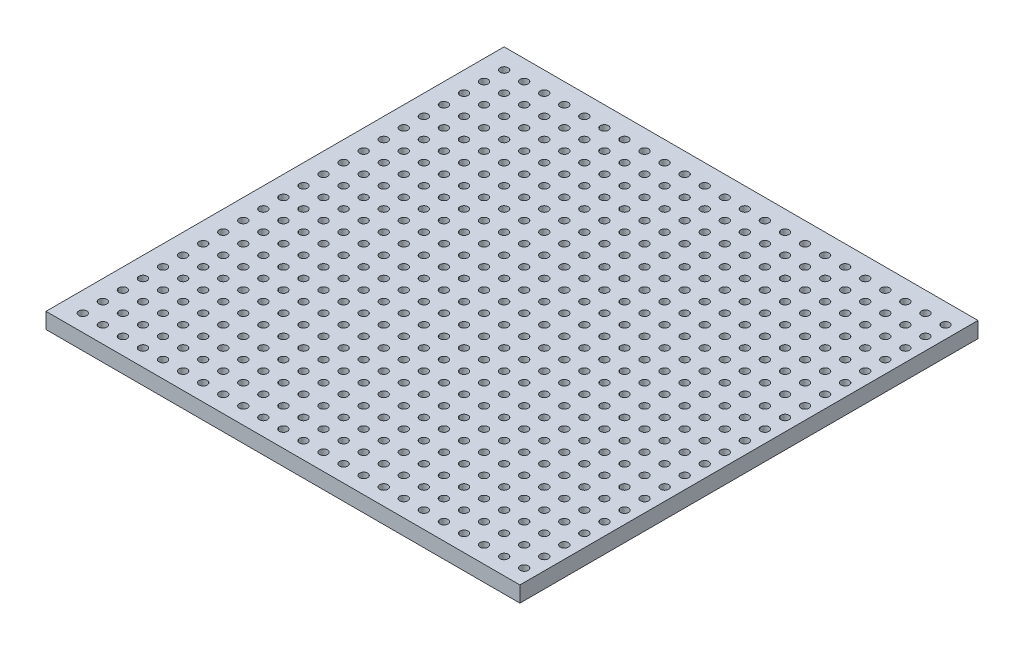
SolidWorks part; units mm, degrees
ref_plane "Front Plane" through (0, 0, 0) normal (0, 0, 1) x (1, 0, 0)
ref_plane "Top Plane" through (0, 0, 0) normal (0, 1, 0) x (1, 0, 0)
ref_plane "Right Plane" through (0, 0, 0) normal (1, 0, 0) x (0, 0, -1)
sketch "Sketch1" plane through (0, 0, 0) normal (0, 1, 0) x (1, 0, 0)
  line L1 (-30, -29) -> (30, -29)
  line L2 (-30, -29) -> (-30, 29)
  line L3 (-30, 29) -> (30, 29)
  line L4 (30, -29) -> (30, 29)
  line L5 (-30, -29) -> (30, 29) construction
  line L6 (-30, 29) -> (30, -29) construction
  point P0 (0, 0)
  dimension "D1" = 58
  dimension "D2" = 60
extrude "Boss-Extrude1" add sketch "Sketch1" along normal blind 2
sketch "Sketch2" plane through (0, 2, 0) normal (0, 1, 0) x (1, 0, 0)
  line L0 (30, 29) -> (-30, 29) construction
  line L1 (-30, 29) -> (-30, -29) construction
  line L2 (-27.46, 26.46) -> (-27.46, -29) construction
  line L3 (-30, -29) -> (30, -29) construction
  circle A0 centre (-27.46, 26.46) radius 0.51
  circle A1 centre (-27.46, 23.92) radius 0.51
  circle A2 centre (-27.46, 21.38) radius 0.51
  circle A3 centre (-27.46, 18.84) radius 0.51
  circle A4 centre (-27.46, 16.3) radius 0.51
  circle A5 centre (-27.46, 13.76) radius 0.51
  circle A6 centre (-27.46, 11.22) radius 0.51
  circle A7 centre (-27.46, 8.68) radius 0.51
  circle A8 centre (-27.46, 6.14) radius 0.51
  circle A9 centre (-27.46, 3.6) radius 0.51
  circle A10 centre (-27.46, 1.06) radius 0.51
  circle A11 centre (-27.46, -1.48) radius 0.51
  circle A12 centre (-24.92, 26.46) radius 0.51
  circle A13 centre (-24.92, 23.92) radius 0.51
  circle A14 centre (-24.92, 21.38) radius 0.51
  circle A15 centre (-24.92, 18.84) radius 0.51
  circle A16 centre (-24.92, 16.3) radius 0.51
  circle A17 centre (-24.92, 13.76) radius 0.51
  circle A18 centre (-24.92, 11.22) radius 0.51
  circle A19 centre (-24.92, 8.68) radius 0.51
  circle A20 centre (-24.92, 6.14) radius 0.51
  circle A21 centre (-24.92, 3.6) radius 0.51
  circle A22 centre (-24.92, 1.06) radius 0.51
  circle A23 centre (-24.92, -1.48) radius 0.51
  circle A24 centre (-22.38, 26.46) radius 0.51
  circle A25 centre (-22.38, 23.92) radius 0.51
  circle A26 centre (-22.38, 21.38) radius 0.51
  circle A27 centre (-22.38, 18.84) radius 0.51
  circle A28 centre (-22.38, 16.3) radius 0.51
  circle A29 centre (-22.38, 13.76) radius 0.51
  circle A30 centre (-22.38, 11.22) radius 0.51
  circle A31 centre (-22.38, 8.68) radius 0.51
  circle A32 centre (-22.38, 6.14) radius 0.51
  circle A33 centre (-22.38, 3.6) radius 0.51
  circle A34 centre (-22.38, 1.06) radius 0.51
  circle A35 centre (-22.38, -1.48) radius 0.51
  circle A36 centre (-19.84, 26.46) radius 0.51
  circle A37 centre (-19.84, 23.92) radius 0.51
  circle A38 centre (-19.84, 21.38) radius 0.51
  circle A39 centre (-19.84, 18.84) radius 0.51
  circle A40 centre (-19.84, 16.3) radius 0.51
  circle A41 centre (-19.84, 13.76) radius 0.51
  circle A42 centre (-19.84, 11.22) radius 0.51
  circle A43 centre (-19.84, 8.68) radius 0.51
  circle A44 centre (-19.84, 6.14) radius 0.51
  circle A45 centre (-19.84, 3.6) radius 0.51
  circle A46 centre (-19.84, 1.06) radius 0.51
  circle A47 centre (-19.84, -1.48) radius 0.51
  circle A48 centre (-17.3, 26.46) radius 0.51
  circle A49 centre (-17.3, 23.92) radius 0.51
  circle A50 centre (-17.3, 21.38) radius 0.51
  circle A51 centre (-17.3, 18.84) radius 0.51
  circle A52 centre (-17.3, 16.3) radius 0.51
  circle A53 centre (-17.3, 13.76) radius 0.51
  circle A54 centre (-17.3, 11.22) radius 0.51
  circle A55 centre (-17.3, 8.68) radius 0.51
  circle A56 centre (-17.3, 6.14) radius 0.51
  circle A57 centre (-17.3, 3.6) radius 0.51
  circle A58 centre (-17.3, 1.06) radius 0.51
  circle A59 centre (-17.3, -1.48) radius 0.51
  circle A60 centre (-14.76, 26.46) radius 0.51
  circle A61 centre (-14.76, 23.92) radius 0.51
  circle A62 centre (-14.76, 21.38) radius 0.51
  circle A63 centre (-14.76, 18.84) radius 0.51
  circle A64 centre (-14.76, 16.3) radius 0.51
  circle A65 centre (-14.76, 13.76) radius 0.51
  circle A66 centre (-14.76, 11.22) radius 0.51
  circle A67 centre (-14.76, 8.68) radius 0.51
  circle A68 centre (-14.76, 6.14) radius 0.51
  circle A69 centre (-14.76, 3.6) radius 0.51
  circle A70 centre (-14.76, 1.06) radius 0.51
  circle A71 centre (-14.76, -1.48) radius 0.51
  circle A72 centre (-12.22, 26.46) radius 0.51
  circle A73 centre (-12.22, 23.92) radius 0.51
  circle A74 centre (-12.22, 21.38) radius 0.51
  circle A75 centre (-12.22, 18.84) radius 0.51
  circle A76 centre (-12.22, 16.3) radius 0.51
  circle A77 centre (-12.22, 13.76) radius 0.51
  circle A78 centre (-12.22, 11.22) radius 0.51
  circle A79 centre (-12.22, 8.68) radius 0.51
  circle A80 centre (-12.22, 6.14) radius 0.51
  circle A81 centre (-12.22, 3.6) radius 0.51
  circle A82 centre (-12.22, 1.06) radius 0.51
  circle A83 centre (-12.22, -1.48) radius 0.51
  circle A84 centre (-9.68, 26.46) radius 0.51
  circle A85 centre (-9.68, 23.92) radius 0.51
  circle A86 centre (-9.68, 21.38) radius 0.51
  circle A87 centre (-9.68, 18.84) radius 0.51
  circle A88 centre (-9.68, 16.3) radius 0.51
  circle A89 centre (-9.68, 13.76) radius 0.51
  circle A90 centre (-9.68, 11.22) radius 0.51
  circle A91 centre (-9.68, 8.68) radius 0.51
  circle A92 centre (-9.68, 6.14) radius 0.51
  circle A93 centre (-9.68, 3.6) radius 0.51
  circle A94 centre (-9.68, 1.06) radius 0.51
  circle A95 centre (-9.68, -1.48) radius 0.51
  circle A96 centre (-7.14, 26.46) radius 0.51
  circle A97 centre (-7.14, 23.92) radius 0.51
  circle A98 centre (-7.14, 21.38) radius 0.51
  circle A99 centre (-7.14, 18.84) radius 0.51
  circle A100 centre (-7.14, 16.3) radius 0.51
  circle A101 centre (-7.14, 13.76) radius 0.51
  circle A102 centre (-7.14, 11.22) radius 0.51
  circle A103 centre (-7.14, 8.68) radius 0.51
  circle A104 centre (-7.14, 6.14) radius 0.51
  circle A105 centre (-7.14, 3.6) radius 0.51
  circle A106 centre (-7.14, 1.06) radius 0.51
  circle A107 centre (-7.14, -1.48) radius 0.51
  circle A108 centre (-4.6, 26.46) radius 0.51
  circle A109 centre (-4.6, 23.92) radius 0.51
  circle A110 centre (-4.6, 21.38) radius 0.51
  circle A111 centre (-4.6, 18.84) radius 0.51
  circle A112 centre (-4.6, 16.3) radius 0.51
  circle A113 centre (-4.6, 13.76) radius 0.51
  circle A114 centre (-4.6, 11.22) radius 0.51
  circle A115 centre (-4.6, 8.68) radius 0.51
  circle A116 centre (-4.6, 6.14) radius 0.51
  circle A117 centre (-4.6, 3.6) radius 0.51
  circle A118 centre (-4.6, 1.06) radius 0.51
  circle A119 centre (-4.6, -1.48) radius 0.51
  circle A120 centre (-2.06, 26.46) radius 0.51
  circle A121 centre (-2.06, 23.92) radius 0.51
  circle A122 centre (-2.06, 21.38) radius 0.51
  circle A123 centre (-2.06, 18.84) radius 0.51
  circle A124 centre (-2.06, 16.3) radius 0.51
  circle A125 centre (-2.06, 13.76) radius 0.51
  circle A126 centre (-2.06, 11.22) radius 0.51
  circle A127 centre (-2.06, 8.68) radius 0.51
  circle A128 centre (-2.06, 6.14) radius 0.51
  circle A129 centre (-2.06, 3.6) radius 0.51
  circle A130 centre (-2.06, 1.06) radius 0.51
  circle A131 centre (-2.06, -1.48) radius 0.51
  circle A132 centre (0.48, 26.46) radius 0.51
  circle A133 centre (0.48, 23.92) radius 0.51
  circle A134 centre (0.48, 21.38) radius 0.51
  circle A135 centre (0.48, 18.84) radius 0.51
  circle A136 centre (0.48, 16.3) radius 0.51
  circle A137 centre (0.48, 13.76) radius 0.51
  circle A138 centre (0.48, 11.22) radius 0.51
  circle A139 centre (0.48, 8.68) radius 0.51
  circle A140 centre (0.48, 6.14) radius 0.51
  circle A141 centre (0.48, 3.6) radius 0.51
  circle A142 centre (0.48, 1.06) radius 0.51
  circle A143 centre (0.48, -1.48) radius 0.51
  circle A144 centre (3.02, 26.46) radius 0.51
  circle A145 centre (3.02, 23.92) radius 0.51
  circle A146 centre (3.02, 21.38) radius 0.51
  circle A147 centre (3.02, 18.84) radius 0.51
  circle A148 centre (3.02, 16.3) radius 0.51
  circle A149 centre (3.02, 13.76) radius 0.51
  circle A150 centre (3.02, 11.22) radius 0.51
  circle A151 centre (3.02, 8.68) radius 0.51
  circle A152 centre (3.02, 6.14) radius 0.51
  circle A153 centre (3.02, 3.6) radius 0.51
  circle A154 centre (3.02, 1.06) radius 0.51
  circle A155 centre (3.02, -1.48) radius 0.51
  circle A156 centre (5.56, 26.46) radius 0.51
  circle A157 centre (5.56, 23.92) radius 0.51
  circle A158 centre (5.56, 21.38) radius 0.51
  circle A159 centre (5.56, 18.84) radius 0.51
  circle A160 centre (5.56, 16.3) radius 0.51
  circle A161 centre (5.56, 13.76) radius 0.51
  circle A162 centre (5.56, 11.22) radius 0.51
  circle A163 centre (5.56, 8.68) radius 0.51
  circle A164 centre (5.56, 6.14) radius 0.51
  circle A165 centre (5.56, 3.6) radius 0.51
  circle A166 centre (5.56, 1.06) radius 0.51
  circle A167 centre (5.56, -1.48) radius 0.51
  circle A168 centre (8.1, 26.46) radius 0.51
  circle A169 centre (8.1, 23.92) radius 0.51
  circle A170 centre (8.1, 21.38) radius 0.51
  circle A171 centre (8.1, 18.84) radius 0.51
  circle A172 centre (8.1, 16.3) radius 0.51
  circle A173 centre (8.1, 13.76) radius 0.51
  circle A174 centre (8.1, 11.22) radius 0.51
  circle A175 centre (8.1, 8.68) radius 0.51
  circle A176 centre (8.1, 6.14) radius 0.51
  circle A177 centre (8.1, 3.6) radius 0.51
  circle A178 centre (8.1, 1.06) radius 0.51
  circle A179 centre (8.1, -1.48) radius 0.51
  circle A180 centre (10.64, 26.46) radius 0.51
  circle A181 centre (10.64, 23.92) radius 0.51
  circle A182 centre (10.64, 21.38) radius 0.51
  circle A183 centre (10.64, 18.84) radius 0.51
  circle A184 centre (10.64, 16.3) radius 0.51
  circle A185 centre (10.64, 13.76) radius 0.51
  circle A186 centre (10.64, 11.22) radius 0.51
  circle A187 centre (10.64, 8.68) radius 0.51
  circle A188 centre (10.64, 6.14) radius 0.51
  circle A189 centre (10.64, 3.6) radius 0.51
  circle A190 centre (10.64, 1.06) radius 0.51
  circle A191 centre (10.64, -1.48) radius 0.51
  circle A192 centre (13.18, 26.46) radius 0.51
  circle A193 centre (13.18, 23.92) radius 0.51
  circle A194 centre (13.18, 21.38) radius 0.51
  circle A195 centre (13.18, 18.84) radius 0.51
  circle A196 centre (13.18, 16.3) radius 0.51
  circle A197 centre (13.18, 13.76) radius 0.51
  circle A198 centre (13.18, 11.22) radius 0.51
  circle A199 centre (13.18, 8.68) radius 0.51
  circle A200 centre (13.18, 6.14) radius 0.51
  circle A201 centre (13.18, 3.6) radius 0.51
  circle A202 centre (13.18, 1.06) radius 0.51
  circle A203 centre (13.18, -1.48) radius 0.51
  circle A204 centre (15.72, 26.46) radius 0.51
  circle A205 centre (15.72, 23.92) radius 0.51
  circle A206 centre (15.72, 21.38) radius 0.51
  circle A207 centre (15.72, 18.84) radius 0.51
  circle A208 centre (15.72, 16.3) radius 0.51
  circle A209 centre (15.72, 13.76) radius 0.51
  circle A210 centre (15.72, 11.22) radius 0.51
  circle A211 centre (15.72, 8.68) radius 0.51
  circle A212 centre (15.72, 6.14) radius 0.51
  circle A213 centre (15.72, 3.6) radius 0.51
  circle A214 centre (15.72, 1.06) radius 0.51
  circle A215 centre (15.72, -1.48) radius 0.51
  circle A216 centre (18.26, 26.46) radius 0.51
  circle A217 centre (18.26, 23.92) radius 0.51
  circle A218 centre (18.26, 21.38) radius 0.51
  circle A219 centre (18.26, 18.84) radius 0.51
  circle A220 centre (18.26, 16.3) radius 0.51
  circle A221 centre (18.26, 13.76) radius 0.51
  circle A222 centre (18.26, 11.22) radius 0.51
  circle A223 centre (18.26, 8.68) radius 0.51
  circle A224 centre (18.26, 6.14) radius 0.51
  circle A225 centre (18.26, 3.6) radius 0.51
  circle A226 centre (18.26, 1.06) radius 0.51
  circle A227 centre (18.26, -1.48) radius 0.51
  circle A228 centre (20.8, 26.46) radius 0.51
  circle A229 centre (20.8, 23.92) radius 0.51
  circle A230 centre (20.8, 21.38) radius 0.51
  circle A231 centre (20.8, 18.84) radius 0.51
  circle A232 centre (20.8, 16.3) radius 0.51
  circle A233 centre (20.8, 13.76) radius 0.51
  circle A234 centre (20.8, 11.22) radius 0.51
  circle A235 centre (20.8, 8.68) radius 0.51
  circle A236 centre (20.8, 6.14) radius 0.51
  circle A237 centre (20.8, 3.6) radius 0.51
  circle A238 centre (20.8, 1.06) radius 0.51
  circle A239 centre (20.8, -1.48) radius 0.51
  circle A240 centre (23.34, 26.46) radius 0.51
  circle A241 centre (23.34, 23.92) radius 0.51
  circle A242 centre (23.34, 21.38) radius 0.51
  circle A243 centre (23.34, 18.84) radius 0.51
  circle A244 centre (23.34, 16.3) radius 0.51
  circle A245 centre (23.34, 13.76) radius 0.51
  circle A246 centre (23.34, 11.22) radius 0.51
  circle A247 centre (23.34, 8.68) radius 0.51
  circle A248 centre (23.34, 6.14) radius 0.51
  circle A249 centre (23.34, 3.6) radius 0.51
  circle A250 centre (23.34, 1.06) radius 0.51
  circle A251 centre (23.34, -1.48) radius 0.51
  circle A252 centre (25.88, 26.46) radius 0.51
  circle A253 centre (25.88, 23.92) radius 0.51
  circle A254 centre (25.88, 21.38) radius 0.51
  circle A255 centre (25.88, 18.84) radius 0.51
  circle A256 centre (25.88, 16.3) radius 0.51
  circle A257 centre (25.88, 13.76) radius 0.51
  circle A258 centre (25.88, 11.22) radius 0.51
  circle A259 centre (25.88, 8.68) radius 0.51
  circle A260 centre (25.88, 6.14) radius 0.51
  circle A261 centre (25.88, 3.6) radius 0.51
  circle A262 centre (25.88, 1.06) radius 0.51
  circle A263 centre (25.88, -1.48) radius 0.51
  circle A264 centre (28.42, 26.46) radius 0.51
  circle A265 centre (28.42, 23.92) radius 0.51
  circle A266 centre (28.42, 21.38) radius 0.51
  circle A267 centre (28.42, 18.84) radius 0.51
  circle A268 centre (28.42, 16.3) radius 0.51
  circle A269 centre (28.42, 13.76) radius 0.51
  circle A270 centre (28.42, 11.22) radius 0.51
  circle A271 centre (28.42, 8.68) radius 0.51
  circle A272 centre (28.42, 6.14) radius 0.51
  circle A273 centre (28.42, 3.6) radius 0.51
  circle A274 centre (28.42, 1.06) radius 0.51
  circle A275 centre (28.42, -1.48) radius 0.51
  circle A300 centre (33.5, 26.46) radius 0.51
  circle A301 centre (33.5, 23.92) radius 0.51
  circle A302 centre (33.5, 21.38) radius 0.51
  circle A303 centre (33.5, 18.84) radius 0.51
  circle A304 centre (33.5, 16.3) radius 0.51
  circle A305 centre (33.5, 13.76) radius 0.51
  circle A306 centre (33.5, 11.22) radius 0.51
  circle A307 centre (33.5, 8.68) radius 0.51
  circle A308 centre (33.5, 6.14) radius 0.51
  circle A309 centre (33.5, 3.6) radius 0.51
  circle A310 centre (33.5, 1.06) radius 0.51
  circle A311 centre (33.5, -1.48) radius 0.51
  circle A312 centre (30.96, 26.46) radius 0.51
  circle A313 centre (30.96, 23.92) radius 0.51
  circle A314 centre (30.96, 21.38) radius 0.51
  circle A315 centre (30.96, 18.84) radius 0.51
  circle A316 centre (30.96, 16.3) radius 0.51
  circle A317 centre (30.96, 13.76) radius 0.51
  circle A318 centre (30.96, 11.22) radius 0.51
  circle A319 centre (30.96, 8.68) radius 0.51
  circle A320 centre (30.96, 6.14) radius 0.51
  circle A321 centre (30.96, 3.6) radius 0.51
  circle A322 centre (30.96, 1.06) radius 0.51
  circle A323 centre (30.96, -1.48) radius 0.51
  circle A324 centre (-27.46, -4.02) radius 0.51
  circle A325 centre (-24.92, -4.02) radius 0.51
  circle A326 centre (-22.38, -4.02) radius 0.51
  circle A327 centre (-19.84, -4.02) radius 0.51
  circle A328 centre (-17.3, -4.02) radius 0.51
  circle A329 centre (-14.76, -4.02) radius 0.51
  circle A330 centre (-12.22, -4.02) radius 0.51
  circle A331 centre (-9.68, -4.02) radius 0.51
  circle A332 centre (-7.14, -4.02) radius 0.51
  circle A333 centre (-4.6, -4.02) radius 0.51
  circle A334 centre (-2.06, -4.02) radius 0.51
  circle A335 centre (0.48, -4.02) radius 0.51
  circle A336 centre (3.02, -4.02) radius 0.51
  circle A337 centre (5.56, -4.02) radius 0.51
  circle A338 centre (8.1, -4.02) radius 0.51
  circle A339 centre (10.64, -4.02) radius 0.51
  circle A340 centre (13.18, -4.02) radius 0.51
  circle A341 centre (15.72, -4.02) radius 0.51
  circle A342 centre (18.26, -4.02) radius 0.51
  circle A343 centre (20.8, -4.02) radius 0.51
  circle A344 centre (23.34, -4.02) radius 0.51
  circle A345 centre (25.88, -4.02) radius 0.51
  circle A346 centre (28.42, -4.02) radius 0.51
  circle A347 centre (-27.46, -6.56) radius 0.51
  circle A348 centre (-24.92, -6.56) radius 0.51
  circle A349 centre (-22.38, -6.56) radius 0.51
  circle A350 centre (-19.84, -6.56) radius 0.51
  circle A351 centre (-17.3, -6.56) radius 0.51
  circle A352 centre (-14.76, -6.56) radius 0.51
  circle A353 centre (-12.22, -6.56) radius 0.51
  circle A354 centre (-9.68, -6.56) radius 0.51
  circle A355 centre (-7.14, -6.56) radius 0.51
  circle A356 centre (-4.6, -6.56) radius 0.51
  circle A357 centre (-2.06, -6.56) radius 0.51
  circle A358 centre (0.48, -6.56) radius 0.51
  circle A359 centre (3.02, -6.56) radius 0.51
  circle A360 centre (5.56, -6.56) radius 0.51
  circle A361 centre (8.1, -6.56) radius 0.51
  circle A362 centre (10.64, -6.56) radius 0.51
  circle A363 centre (13.18, -6.56) radius 0.51
  circle A364 centre (15.72, -6.56) radius 0.51
  circle A365 centre (18.26, -6.56) radius 0.51
  circle A366 centre (20.8, -6.56) radius 0.51
  circle A367 centre (23.34, -6.56) radius 0.51
  circle A368 centre (25.88, -6.56) radius 0.51
  circle A369 centre (28.42, -6.56) radius 0.51
  circle A370 centre (-27.46, -9.1) radius 0.51
  circle A371 centre (-24.92, -9.1) radius 0.51
  circle A372 centre (-22.38, -9.1) radius 0.51
  circle A373 centre (-19.84, -9.1) radius 0.51
  circle A374 centre (-17.3, -9.1) radius 0.51
  circle A375 centre (-14.76, -9.1) radius 0.51
  circle A376 centre (-12.22, -9.1) radius 0.51
  circle A377 centre (-9.68, -9.1) radius 0.51
  circle A378 centre (-7.14, -9.1) radius 0.51
  circle A379 centre (-4.6, -9.1) radius 0.51
  circle A380 centre (-2.06, -9.1) radius 0.51
  circle A381 centre (0.48, -9.1) radius 0.51
  circle A382 centre (3.02, -9.1) radius 0.51
  circle A383 centre (5.56, -9.1) radius 0.51
  circle A384 centre (8.1, -9.1) radius 0.51
  circle A385 centre (10.64, -9.1) radius 0.51
  circle A386 centre (13.18, -9.1) radius 0.51
  circle A387 centre (15.72, -9.1) radius 0.51
  circle A388 centre (18.26, -9.1) radius 0.51
  circle A389 centre (20.8, -9.1) radius 0.51
  circle A390 centre (23.34, -9.1) radius 0.51
  circle A391 centre (25.88, -9.1) radius 0.51
  circle A392 centre (28.42, -9.1) radius 0.51
  circle A393 centre (-27.46, -11.64) radius 0.51
  circle A394 centre (-24.92, -11.64) radius 0.51
  circle A395 centre (-22.38, -11.64) radius 0.51
  circle A396 centre (-19.84, -11.64) radius 0.51
  circle A397 centre (-17.3, -11.64) radius 0.51
  circle A398 centre (-14.76, -11.64) radius 0.51
  circle A399 centre (-12.22, -11.64) radius 0.51
  circle A400 centre (-9.68, -11.64) radius 0.51
  circle A401 centre (-7.14, -11.64) radius 0.51
  circle A402 centre (-4.6, -11.64) radius 0.51
  circle A403 centre (-2.06, -11.64) radius 0.51
  circle A404 centre (0.48, -11.64) radius 0.51
  circle A405 centre (3.02, -11.64) radius 0.51
  circle A406 centre (5.56, -11.64) radius 0.51
  circle A407 centre (8.1, -11.64) radius 0.51
  circle A408 centre (10.64, -11.64) radius 0.51
  circle A409 centre (13.18, -11.64) radius 0.51
  circle A410 centre (15.72, -11.64) radius 0.51
  circle A411 centre (18.26, -11.64) radius 0.51
  circle A412 centre (20.8, -11.64) radius 0.51
  circle A413 centre (23.34, -11.64) radius 0.51
  circle A414 centre (25.88, -11.64) radius 0.51
  circle A415 centre (28.42, -11.64) radius 0.51
  circle A416 centre (-27.46, -14.18) radius 0.51
  circle A417 centre (-24.92, -14.18) radius 0.51
  circle A418 centre (-22.38, -14.18) radius 0.51
  circle A419 centre (-19.84, -14.18) radius 0.51
  circle A420 centre (-17.3, -14.18) radius 0.51
  circle A421 centre (-14.76, -14.18) radius 0.51
  circle A422 centre (-12.22, -14.18) radius 0.51
  circle A423 centre (-9.68, -14.18) radius 0.51
  circle A424 centre (-7.14, -14.18) radius 0.51
  circle A425 centre (-4.6, -14.18) radius 0.51
  circle A426 centre (-2.06, -14.18) radius 0.51
  circle A427 centre (0.48, -14.18) radius 0.51
  circle A428 centre (3.02, -14.18) radius 0.51
  circle A429 centre (5.56, -14.18) radius 0.51
  circle A430 centre (8.1, -14.18) radius 0.51
  circle A431 centre (10.64, -14.18) radius 0.51
  circle A432 centre (13.18, -14.18) radius 0.51
  circle A433 centre (15.72, -14.18) radius 0.51
  circle A434 centre (18.26, -14.18) radius 0.51
  circle A435 centre (20.8, -14.18) radius 0.51
  circle A436 centre (23.34, -14.18) radius 0.51
  circle A437 centre (25.88, -14.18) radius 0.51
  circle A438 centre (28.42, -14.18) radius 0.51
  circle A439 centre (-27.46, -16.72) radius 0.51
  circle A440 centre (-24.92, -16.72) radius 0.51
  circle A441 centre (-22.38, -16.72) radius 0.51
  circle A442 centre (-19.84, -16.72) radius 0.51
  circle A443 centre (-17.3, -16.72) radius 0.51
  circle A444 centre (-14.76, -16.72) radius 0.51
  circle A445 centre (-12.22, -16.72) radius 0.51
  circle A446 centre (-9.68, -16.72) radius 0.51
  circle A447 centre (-7.14, -16.72) radius 0.51
  circle A448 centre (-4.6, -16.72) radius 0.51
  circle A449 centre (-2.06, -16.72) radius 0.51
  circle A450 centre (0.48, -16.72) radius 0.51
  circle A451 centre (3.02, -16.72) radius 0.51
  circle A452 centre (5.56, -16.72) radius 0.51
  circle A453 centre (8.1, -16.72) radius 0.51
  circle A454 centre (10.64, -16.72) radius 0.51
  circle A455 centre (13.18, -16.72) radius 0.51
  circle A456 centre (15.72, -16.72) radius 0.51
  circle A457 centre (18.26, -16.72) radius 0.51
  circle A458 centre (20.8, -16.72) radius 0.51
  circle A459 centre (23.34, -16.72) radius 0.51
  circle A460 centre (25.88, -16.72) radius 0.51
  circle A461 centre (28.42, -16.72) radius 0.51
  circle A462 centre (-27.46, -19.26) radius 0.51
  circle A463 centre (-24.92, -19.26) radius 0.51
  circle A464 centre (-22.38, -19.26) radius 0.51
  circle A465 centre (-19.84, -19.26) radius 0.51
  circle A466 centre (-17.3, -19.26) radius 0.51
  circle A467 centre (-14.76, -19.26) radius 0.51
  circle A468 centre (-12.22, -19.26) radius 0.51
  circle A469 centre (-9.68, -19.26) radius 0.51
  circle A470 centre (-7.14, -19.26) radius 0.51
  circle A471 centre (-4.6, -19.26) radius 0.51
  circle A472 centre (-2.06, -19.26) radius 0.51
  circle A473 centre (0.48, -19.26) radius 0.51
  circle A474 centre (3.02, -19.26) radius 0.51
  circle A475 centre (5.56, -19.26) radius 0.51
  circle A476 centre (8.1, -19.26) radius 0.51
  circle A477 centre (10.64, -19.26) radius 0.51
  circle A478 centre (13.18, -19.26) radius 0.51
  circle A479 centre (15.72, -19.26) radius 0.51
  circle A480 centre (18.26, -19.26) radius 0.51
  circle A481 centre (20.8, -19.26) radius 0.51
  circle A482 centre (23.34, -19.26) radius 0.51
  circle A483 centre (25.88, -19.26) radius 0.51
  circle A484 centre (28.42, -19.26) radius 0.51
  circle A485 centre (-27.46, -21.8) radius 0.51
  circle A486 centre (-24.92, -21.8) radius 0.51
  circle A487 centre (-22.38, -21.8) radius 0.51
  circle A488 centre (-19.84, -21.8) radius 0.51
  circle A489 centre (-17.3, -21.8) radius 0.51
  circle A490 centre (-14.76, -21.8) radius 0.51
  circle A491 centre (-12.22, -21.8) radius 0.51
  circle A492 centre (-9.68, -21.8) radius 0.51
  circle A493 centre (-7.14, -21.8) radius 0.51
  circle A494 centre (-4.6, -21.8) radius 0.51
  circle A495 centre (-2.06, -21.8) radius 0.51
  circle A496 centre (0.48, -21.8) radius 0.51
  circle A497 centre (3.02, -21.8) radius 0.51
  circle A498 centre (5.56, -21.8) radius 0.51
  circle A499 centre (8.1, -21.8) radius 0.51
  circle A500 centre (10.64, -21.8) radius 0.51
  circle A501 centre (13.18, -21.8) radius 0.51
  circle A502 centre (15.72, -21.8) radius 0.51
  circle A503 centre (18.26, -21.8) radius 0.51
  circle A504 centre (20.8, -21.8) radius 0.51
  circle A505 centre (23.34, -21.8) radius 0.51
  circle A506 centre (25.88, -21.8) radius 0.51
  circle A507 centre (28.42, -21.8) radius 0.51
  circle A508 centre (-27.46, -24.34) radius 0.51
  circle A509 centre (-24.92, -24.34) radius 0.51
  circle A510 centre (-22.38, -24.34) radius 0.51
  circle A511 centre (-19.84, -24.34) radius 0.51
  circle A512 centre (-17.3, -24.34) radius 0.51
  circle A513 centre (-14.76, -24.34) radius 0.51
  circle A514 centre (-12.22, -24.34) radius 0.51
  circle A515 centre (-9.68, -24.34) radius 0.51
  circle A516 centre (-7.14, -24.34) radius 0.51
  circle A517 centre (-4.6, -24.34) radius 0.51
  circle A518 centre (-2.06, -24.34) radius 0.51
  circle A519 centre (0.48, -24.34) radius 0.51
  circle A520 centre (3.02, -24.34) radius 0.51
  circle A521 centre (5.56, -24.34) radius 0.51
  circle A522 centre (8.1, -24.34) radius 0.51
  circle A523 centre (10.64, -24.34) radius 0.51
  circle A524 centre (13.18, -24.34) radius 0.51
  circle A525 centre (15.72, -24.34) radius 0.51
  circle A526 centre (18.26, -24.34) radius 0.51
  circle A527 centre (20.8, -24.34) radius 0.51
  circle A528 centre (23.34, -24.34) radius 0.51
  circle A529 centre (25.88, -24.34) radius 0.51
  circle A530 centre (28.42, -24.34) radius 0.51
  circle A531 centre (-27.46, -26.88) radius 0.51
  circle A532 centre (-24.92, -26.88) radius 0.51
  circle A533 centre (-22.38, -26.88) radius 0.51
  circle A534 centre (-19.84, -26.88) radius 0.51
  circle A535 centre (-17.3, -26.88) radius 0.51
  circle A536 centre (-14.76, -26.88) radius 0.51
  circle A537 centre (-12.22, -26.88) radius 0.51
  circle A538 centre (-9.68, -26.88) radius 0.51
  circle A539 centre (-7.14, -26.88) radius 0.51
  circle A540 centre (-4.6, -26.88) radius 0.51
  circle A541 centre (-2.06, -26.88) radius 0.51
  circle A542 centre (0.48, -26.88) radius 0.51
  circle A543 centre (3.02, -26.88) radius 0.51
  circle A544 centre (5.56, -26.88) radius 0.51
  circle A545 centre (8.1, -26.88) radius 0.51
  circle A546 centre (10.64, -26.88) radius 0.51
  circle A547 centre (13.18, -26.88) radius 0.51
  circle A548 centre (15.72, -26.88) radius 0.51
  circle A549 centre (18.26, -26.88) radius 0.51
  circle A550 centre (20.8, -26.88) radius 0.51
  circle A551 centre (23.34, -26.88) radius 0.51
  circle A552 centre (25.88, -26.88) radius 0.51
  circle A553 centre (28.42, -26.88) radius 0.51
  circle A761 centre (-27.46, -29.42) radius 0.51
  circle A762 centre (-24.92, -29.42) radius 0.51
  circle A763 centre (-22.38, -29.42) radius 0.51
  circle A764 centre (-19.84, -29.42) radius 0.51
  circle A765 centre (-17.3, -29.42) radius 0.51
  circle A766 centre (-14.76, -29.42) radius 0.51
  circle A767 centre (-12.22, -29.42) radius 0.51
  circle A768 centre (-9.68, -29.42) radius 0.51
  circle A769 centre (-7.14, -29.42) radius 0.51
  circle A770 centre (-4.6, -29.42) radius 0.51
  circle A771 centre (-2.06, -29.42) radius 0.51
  circle A772 centre (0.48, -29.42) radius 0.51
  circle A773 centre (3.02, -29.42) radius 0.51
  circle A774 centre (5.56, -29.42) radius 0.51
  circle A775 centre (8.1, -29.42) radius 0.51
  circle A776 centre (10.64, -29.42) radius 0.51
  circle A777 centre (13.18, -29.42) radius 0.51
  circle A778 centre (15.72, -29.42) radius 0.51
  circle A779 centre (18.26, -29.42) radius 0.51
  circle A780 centre (20.8, -29.42) radius 0.51
  circle A781 centre (23.34, -29.42) radius 0.51
  circle A782 centre (25.88, -29.42) radius 0.51
  circle A783 centre (28.42, -29.42) radius 0.51
  circle A784 centre (-27.46, -31.96) radius 0.51
  circle A785 centre (-24.92, -31.96) radius 0.51
  circle A786 centre (-22.38, -31.96) radius 0.51
  circle A787 centre (-19.84, -31.96) radius 0.51
  circle A788 centre (-17.3, -31.96) radius 0.51
  circle A789 centre (-14.76, -31.96) radius 0.51
  circle A790 centre (-12.22, -31.96) radius 0.51
  circle A791 centre (-9.68, -31.96) radius 0.51
  circle A792 centre (-7.14, -31.96) radius 0.51
  circle A793 centre (-4.6, -31.96) radius 0.51
  circle A794 centre (-2.06, -31.96) radius 0.51
  circle A795 centre (0.48, -31.96) radius 0.51
  circle A796 centre (3.02, -31.96) radius 0.51
  circle A797 centre (5.56, -31.96) radius 0.51
  circle A798 centre (8.1, -31.96) radius 0.51
  circle A799 centre (10.64, -31.96) radius 0.51
  circle A800 centre (13.18, -31.96) radius 0.51
  circle A801 centre (15.72, -31.96) radius 0.51
  circle A802 centre (18.26, -31.96) radius 0.51
  circle A803 centre (20.8, -31.96) radius 0.51
  circle A804 centre (23.34, -31.96) radius 0.51
  circle A805 centre (25.88, -31.96) radius 0.51
  circle A806 centre (28.42, -31.96) radius 0.51
  circle A807 centre (-27.46, -34.5) radius 0.51
  circle A808 centre (-24.92, -34.5) radius 0.51
  circle A809 centre (-22.38, -34.5) radius 0.51
  circle A810 centre (-19.84, -34.5) radius 0.51
  circle A811 centre (-17.3, -34.5) radius 0.51
  circle A812 centre (-14.76, -34.5) radius 0.51
  circle A813 centre (-12.22, -34.5) radius 0.51
  circle A814 centre (-9.68, -34.5) radius 0.51
  circle A815 centre (-7.14, -34.5) radius 0.51
  circle A816 centre (-4.6, -34.5) radius 0.51
  circle A817 centre (-2.06, -34.5) radius 0.51
  circle A818 centre (0.48, -34.5) radius 0.51
  circle A819 centre (3.02, -34.5) radius 0.51
  circle A820 centre (5.56, -34.5) radius 0.51
  circle A821 centre (8.1, -34.5) radius 0.51
  circle A822 centre (10.64, -34.5) radius 0.51
  circle A823 centre (13.18, -34.5) radius 0.51
  circle A824 centre (15.72, -34.5) radius 0.51
  circle A825 centre (18.26, -34.5) radius 0.51
  circle A826 centre (20.8, -34.5) radius 0.51
  circle A827 centre (23.34, -34.5) radius 0.51
  circle A828 centre (25.88, -34.5) radius 0.51
  circle A829 centre (28.42, -34.5) radius 0.51
  circle A830 centre (-27.46, -37.04) radius 0.51
  circle A831 centre (-24.92, -37.04) radius 0.51
  circle A832 centre (-22.38, -37.04) radius 0.51
  circle A833 centre (-19.84, -37.04) radius 0.51
  circle A834 centre (-17.3, -37.04) radius 0.51
  circle A835 centre (-14.76, -37.04) radius 0.51
  circle A836 centre (-12.22, -37.04) radius 0.51
  circle A837 centre (-9.68, -37.04) radius 0.51
  circle A838 centre (-7.14, -37.04) radius 0.51
  circle A839 centre (-4.6, -37.04) radius 0.51
  circle A840 centre (-2.06, -37.04) radius 0.51
  circle A841 centre (0.48, -37.04) radius 0.51
  circle A842 centre (3.02, -37.04) radius 0.51
  circle A843 centre (5.56, -37.04) radius 0.51
  circle A844 centre (8.1, -37.04) radius 0.51
  circle A845 centre (10.64, -37.04) radius 0.51
  circle A846 centre (13.18, -37.04) radius 0.51
  circle A847 centre (15.72, -37.04) radius 0.51
  circle A848 centre (18.26, -37.04) radius 0.51
  circle A849 centre (20.8, -37.04) radius 0.51
  circle A850 centre (23.34, -37.04) radius 0.51
  circle A851 centre (25.88, -37.04) radius 0.51
  circle A852 centre (28.42, -37.04) radius 0.51
  circle A853 centre (-27.46, -39.58) radius 0.51
  circle A854 centre (-24.92, -39.58) radius 0.51
  circle A855 centre (-22.38, -39.58) radius 0.51
  circle A856 centre (-19.84, -39.58) radius 0.51
  circle A857 centre (-17.3, -39.58) radius 0.51
  circle A858 centre (-14.76, -39.58) radius 0.51
  circle A859 centre (-12.22, -39.58) radius 0.51
  circle A860 centre (-9.68, -39.58) radius 0.51
  circle A861 centre (-7.14, -39.58) radius 0.51
  circle A862 centre (-4.6, -39.58) radius 0.51
  circle A863 centre (-2.06, -39.58) radius 0.51
  circle A864 centre (0.48, -39.58) radius 0.51
  circle A865 centre (3.02, -39.58) radius 0.51
  circle A866 centre (5.56, -39.58) radius 0.51
  circle A867 centre (8.1, -39.58) radius 0.51
  circle A868 centre (10.64, -39.58) radius 0.51
  circle A869 centre (13.18, -39.58) radius 0.51
  circle A870 centre (15.72, -39.58) radius 0.51
  circle A871 centre (18.26, -39.58) radius 0.51
  circle A872 centre (20.8, -39.58) radius 0.51
  circle A873 centre (23.34, -39.58) radius 0.51
  circle A874 centre (25.88, -39.58) radius 0.51
  circle A875 centre (28.42, -39.58) radius 0.51
  circle A876 centre (-27.46, -42.12) radius 0.51
  circle A877 centre (-24.92, -42.12) radius 0.51
  circle A878 centre (-22.38, -42.12) radius 0.51
  circle A879 centre (-19.84, -42.12) radius 0.51
  circle A880 centre (-17.3, -42.12) radius 0.51
  circle A881 centre (-14.76, -42.12) radius 0.51
  circle A882 centre (-12.22, -42.12) radius 0.51
  circle A883 centre (-9.68, -42.12) radius 0.51
  circle A884 centre (-7.14, -42.12) radius 0.51
  circle A885 centre (-4.6, -42.12) radius 0.51
  circle A886 centre (-2.06, -42.12) radius 0.51
  circle A887 centre (0.48, -42.12) radius 0.51
  circle A888 centre (3.02, -42.12) radius 0.51
  circle A889 centre (5.56, -42.12) radius 0.51
  circle A890 centre (8.1, -42.12) radius 0.51
  circle A891 centre (10.64, -42.12) radius 0.51
  circle A892 centre (13.18, -42.12) radius 0.51
  circle A893 centre (15.72, -42.12) radius 0.51
  circle A894 centre (18.26, -42.12) radius 0.51
  circle A895 centre (20.8, -42.12) radius 0.51
  circle A896 centre (23.34, -42.12) radius 0.51
  circle A897 centre (25.88, -42.12) radius 0.51
  circle A898 centre (28.42, -42.12) radius 0.51
  circle A899 centre (-27.46, -44.66) radius 0.51
  circle A900 centre (-24.92, -44.66) radius 0.51
  circle A901 centre (-22.38, -44.66) radius 0.51
  circle A902 centre (-19.84, -44.66) radius 0.51
  circle A903 centre (-17.3, -44.66) radius 0.51
  circle A904 centre (-14.76, -44.66) radius 0.51
  circle A905 centre (-12.22, -44.66) radius 0.51
  circle A906 centre (-9.68, -44.66) radius 0.51
  circle A907 centre (-7.14, -44.66) radius 0.51
  circle A908 centre (-4.6, -44.66) radius 0.51
  circle A909 centre (-2.06, -44.66) radius 0.51
  circle A910 centre (0.48, -44.66) radius 0.51
  circle A911 centre (3.02, -44.66) radius 0.51
  circle A912 centre (5.56, -44.66) radius 0.51
  circle A913 centre (8.1, -44.66) radius 0.51
  circle A914 centre (10.64, -44.66) radius 0.51
  circle A915 centre (13.18, -44.66) radius 0.51
  circle A916 centre (15.72, -44.66) radius 0.51
  circle A917 centre (18.26, -44.66) radius 0.51
  circle A918 centre (20.8, -44.66) radius 0.51
  circle A919 centre (23.34, -44.66) radius 0.51
  circle A920 centre (25.88, -44.66) radius 0.51
  circle A921 centre (28.42, -44.66) radius 0.51
  circle A922 centre (-27.46, -47.2) radius 0.51
  circle A923 centre (-24.92, -47.2) radius 0.51
  circle A924 centre (-22.38, -47.2) radius 0.51
  circle A925 centre (-19.84, -47.2) radius 0.51
  circle A926 centre (-17.3, -47.2) radius 0.51
  circle A927 centre (-14.76, -47.2) radius 0.51
  circle A928 centre (-12.22, -47.2) radius 0.51
  circle A929 centre (-9.68, -47.2) radius 0.51
  circle A930 centre (-7.14, -47.2) radius 0.51
  circle A931 centre (-4.6, -47.2) radius 0.51
  circle A932 centre (-2.06, -47.2) radius 0.51
  circle A933 centre (0.48, -47.2) radius 0.51
  circle A934 centre (3.02, -47.2) radius 0.51
  circle A935 centre (5.56, -47.2) radius 0.51
  circle A936 centre (8.1, -47.2) radius 0.51
  circle A937 centre (10.64, -47.2) radius 0.51
  circle A938 centre (13.18, -47.2) radius 0.51
  circle A939 centre (15.72, -47.2) radius 0.51
  circle A940 centre (18.26, -47.2) radius 0.51
  circle A941 centre (20.8, -47.2) radius 0.51
  circle A942 centre (23.34, -47.2) radius 0.51
  circle A943 centre (25.88, -47.2) radius 0.51
  circle A944 centre (28.42, -47.2) radius 0.51
  circle A945 centre (-27.46, -49.74) radius 0.51
  circle A946 centre (-24.92, -49.74) radius 0.51
  circle A947 centre (-22.38, -49.74) radius 0.51
  circle A948 centre (-19.84, -49.74) radius 0.51
  circle A949 centre (-17.3, -49.74) radius 0.51
  circle A950 centre (-14.76, -49.74) radius 0.51
  circle A951 centre (-12.22, -49.74) radius 0.51
  circle A952 centre (-9.68, -49.74) radius 0.51
  circle A953 centre (-7.14, -49.74) radius 0.51
  circle A954 centre (-4.6, -49.74) radius 0.51
  circle A955 centre (-2.06, -49.74) radius 0.51
  circle A956 centre (0.48, -49.74) radius 0.51
  circle A957 centre (3.02, -49.74) radius 0.51
  circle A958 centre (5.56, -49.74) radius 0.51
  circle A959 centre (8.1, -49.74) radius 0.51
  circle A960 centre (10.64, -49.74) radius 0.51
  circle A961 centre (13.18, -49.74) radius 0.51
  circle A962 centre (15.72, -49.74) radius 0.51
  circle A963 centre (18.26, -49.74) radius 0.51
  circle A964 centre (20.8, -49.74) radius 0.51
  circle A965 centre (23.34, -49.74) radius 0.51
  circle A966 centre (25.88, -49.74) radius 0.51
  circle A967 centre (28.42, -49.74) radius 0.51
  dimension "D1" = 2.54
  dimension "D3" = 1.02
  dimension "D5" = 2.54
  dimension "D6" = 2.54
  dimension "D8" = 2.54
  dimension "D9" = 2.54
  dimension "D10" = 2.54
  dimension "D11" = 2.54
  dimension "D12" = 2.54
  dimension "D13" = 2.54
  dimension "D2" = 2.54
  dimension "D4" = 2.54
  dimension "D7" = 2.54
  dimension "D14" = 2.54
  dimension "D15" = 2.54
  dimension "D16" = 25
  dimension "D17" = 20
extrude "Cut-Extrude1" cut sketch "Sketch2" against normal blind 2
